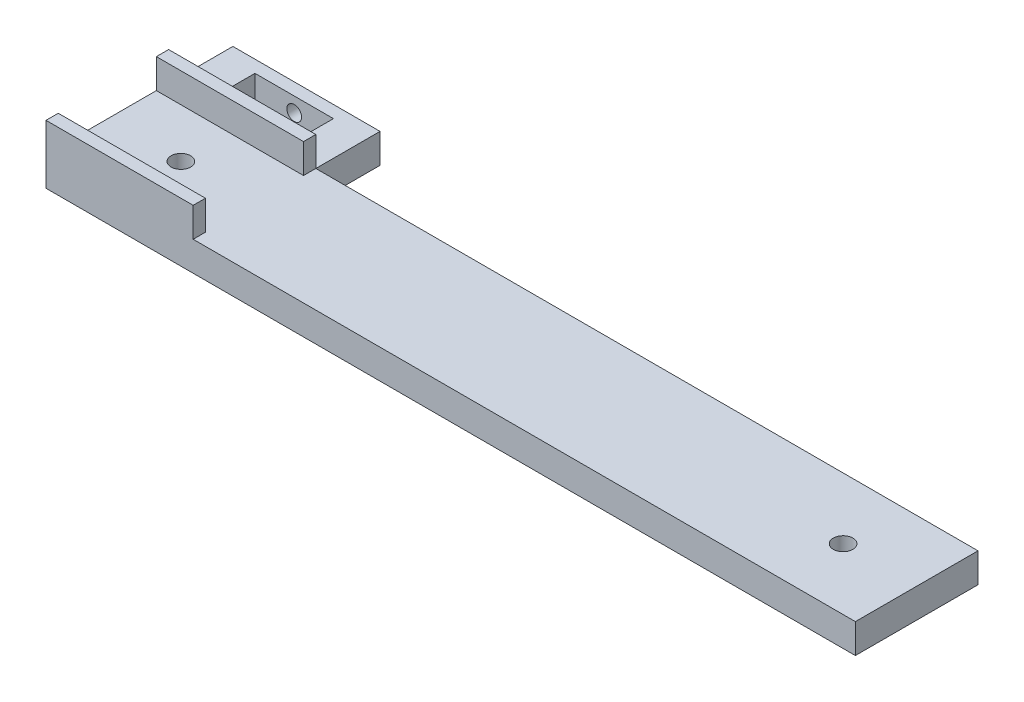
SolidWorks part; units mm, degrees
ref_plane "Front" through (0, 0, 0) normal (0, 0, 1) x (1, 0, 0)
ref_plane "Top" through (0, 0, 0) normal (0, 1, 0) x (1, 0, 0)
ref_plane "Right" through (0, 0, 0) normal (1, 0, 0) x (0, 0, -1)
sketch "Sketch1" plane through (0, 0, 0) normal (0, 1, 0) x (1, 0, 0)
  line L0 (0, -20) -> (0, -22.5)
  line L1 (0, 0) -> (-30, 0)
  line L2 (0, 0) -> (0, -20)
  line L3 (0, -20) -> (-30, -20)
  line L4 (-30, 0) -> (-30, -20)
  line L5 (0, -22.5) -> (-30, -22.5)
  line L6 (-30, -22.5) -> (-30, -20)
  line L7 (0, 0) -> (-7, 0)
  line L8 (-30, 0) -> (0, 0)
  line L9 (-30, 0) -> (-30, 2.5)
  line L10 (-30, 2.5) -> (0, 2.5)
  line L11 (0, 0) -> (0, 2.5)
  line L12 (-30, 0) -> (-23, 0)
  line L13 (-30, 2.5) -> (-30, 13.1)
  line L14 (-30, 13.1) -> (0, 13.1)
  line L15 (0, 13.1) -> (0, 2.5)
  line L16 (0, 13.1) -> (0, 15.6)
  line L17 (0, 15.6) -> (-30, 15.6)
  line L18 (-30, 15.6) -> (-30, 13.1)
  line L19 (-7, 0) -> (-7, 15.6)
  line L20 (-23, 0) -> (-23, 15.6)
  line L21 (-15, -20) -> (-15, 0)
  line L22 (-15, 0) -> (-15, -10)
  line L23 (-15, -10) -> (-165, -10)
  line L24 (-165, -10) -> (-165, -22.5)
  line L25 (-165, -22.5) -> (-165, 2.5)
  line L26 (-165, 2.5) -> (-30, 2.5)
  line L27 (-165, -22.5) -> (-30, -22.5)
  line L28 (-165, -10) -> (-150, -10)
  line L29 (135, -22.5) -> (135, 2.5)
  line L30 (135, 2.5) -> (0, 2.5)
  line L31 (135, -22.5) -> (0, -22.5)
  circle A0 centre (-150, -10) radius 2
  circle A1 centre (120, -10) radius 2
  dimension "D10" = 15
  dimension "D1" = 20
  dimension "D2" = 2.5
  dimension "D3" = 2.5
  dimension "D4" = 30
  dimension "D5" = 7
  dimension "D6" = 7
  dimension "D7" = 10.6
  dimension "D8" = 2.5
  dimension "D9" = 150
extrude "Boss-Extrude1" add sketch "Sketch1" along normal blind 6 contours L1 L8 L4 L3 L2 | L6 L5 L0 L3 | L20 L1 L19 L10 | L19 L1 L11 L10 | L19 L10 L15 L14 | L19 L14 L16 L17 | L20 L14 L19 L17 | L14 L20 L17 L18 | L10 L20 L14 L13 | L8 L20 L10 L9 | L21 L23 L4 L3 | L23 L21 L8 L4 | L31 L29 L30 L11 L2 L0 A1 region at (67.3038, 0, 10) region at (-7.5, 0, 10) region at (-15, 0, 21.25) region at (-3.5, 0, -1.25) region at (-22.5, 0, 15) region at (-15, 0, -1.25) region at (-3.5, 0, -7.8) region at (-22.5, 0, 5) region at (-3.5, 0, -14.35) region at (-26.5, 0, -1.25) region at (-26.5, 0, -7.8) region at (-15, 0, -14.35) region at (-26.5, 0, -14.35)
extrude "Boss-Extrude2" add sketch "Sketch1<3>" along normal blind 12 contours L19 L1 L11 L10 | L20 L1 L19 L10 | L6 L5 L0 L3 | L8 L20 L10 L9 region at (-15, 0, 21.25) region at (-3.5, 0, -1.25) region at (-15, 0, -1.25) region at (-26.5, 0, -1.25)
sketch "Sketch1<3>" plane through (0, 0, 0) normal (0, 1, 0) x (1, 0, 0) same geometry as "Sketch1"
sketch "Sketch3" plane through (0, 0, -15.6) normal (0, 0, -1) x (-1, 0, 0)
  line L0 (30, 3) -> (23, 3)
  line L1 (30, 6) -> (30, 0) construction
  line L2 (23, 3) -> (15, 3)
  circle A0 centre (15, 3) radius 1.5
  dimension "D1" = 7
  dimension "D2" = 8
extrude "Cut-Extrude2" cut sketch "Sketch3" against normal blind 15.5 contours A0
sketch "Sketch4" plane through (0, 0, -2.5) normal (0, 0, -1) x (-1, 0, 0)
  line L0 (23, 3) -> (15, 3)
  line L1 (23, 6) -> (23, 0) construction
  line L3 (17.8868, 3) -> (16.4434, 5.5)
  line L4 (16.4434, 5.5) -> (13.5566, 5.5)
  line L5 (13.5566, 5.5) -> (12.1132, 3)
  line L6 (12.1132, 3) -> (13.5566, 0.5)
  line L7 (13.5566, 0.5) -> (16.4434, 0.5)
  line L8 (16.4434, 0.5) -> (17.8868, 3)
  circle A0 centre (15, 3) radius 2.5 construction
  dimension "D1" = 8
sketch "Sketch2" plane through (0, 6, 0) normal (0, 1, 0) x (1, 0, 0)
  line L0 (-30, -10) -> (0, -10)
  line L1 (-30, 15.6) -> (-30, 2.5) construction
  line L2 (0, 0) -> (0, -20) construction
  circle A0 centre (-15, -10) radius 2
extrude "Cut-Extrude1" cut sketch "Sketch2" against normal through all contours L0 A0 | L0 A0 region at (-15, 6, 9.1512) region at (-15, 6, 10.8488)
